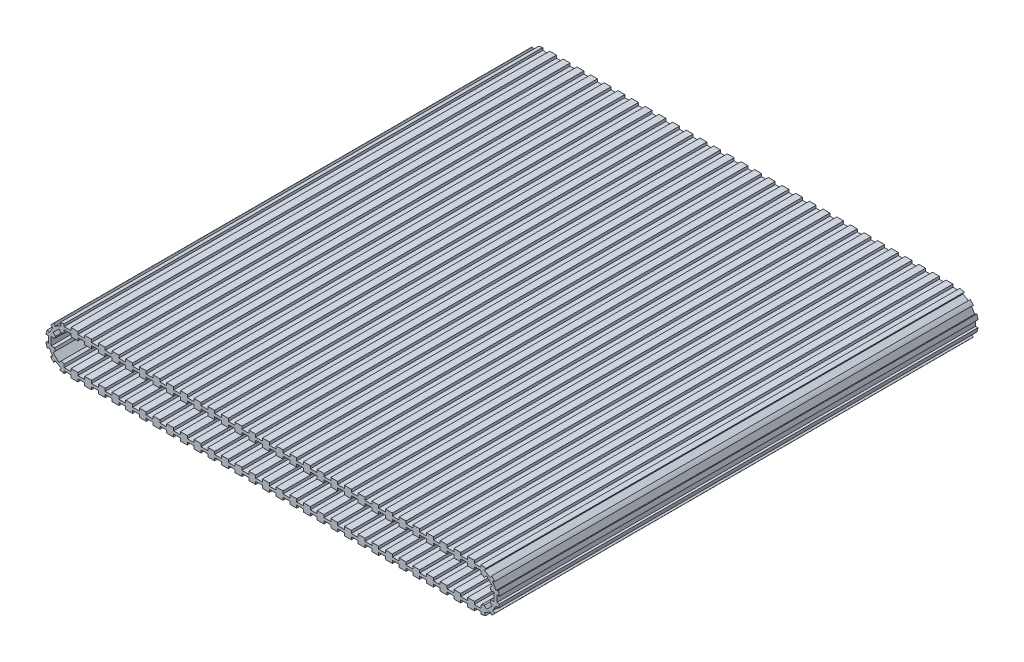
SolidWorks part; units mm, degrees
ref_plane "前视基准面" through (0, 0, 0) normal (0, 0, 1) x (1, 0, 0)
ref_plane "上视基准面" through (0, 0, 0) normal (0, 1, 0) x (1, 0, 0)
ref_plane "右视基准面" through (0, 0, 0) normal (1, 0, 0) x (0, 0, -1)
sketch "草图1" plane through (0, 0, 0) normal (0, 0, 1) x (1, 0, 0)
  line L0 (-150, 0) -> (150, 0) construction
  line L1 (-150, 10) -> (150, 10)
  line L2 (-150, -10) -> (150, -10)
  line L3 (-150, 0) -> (150, 0) construction
  line L4 (-150, 16) -> (150, 16)
  line L5 (-150, -16) -> (150, -16)
  arc A0 (-150, 10) -> (-150, -10) centre (-150, 0) ccw
  arc A1 (150, -10) -> (150, 10) centre (150, 0) ccw
  arc A2 (-150, 16) -> (-150, -16) centre (-150, 0) ccw
  arc A3 (150, -16) -> (150, 16) centre (150, 0) ccw
  point P3 (0, 0)
  point P8 (0, 0)
  dimension "D1" = 10
  dimension "D2" = 16
  dimension "D3" = 300
extrude "凸台-拉伸1" add sketch "草图1" along normal mid plane 350
sketch "草图2" plane through (0, 16, 0) normal (0, 1, 0) x (1, 0, 0)
  line L0 (150, -175) -> (-150, -175) construction
  line L5 (0, -175) -> (0, 175) construction
  line L6 (-2.5, 0) -> (2.5, 0) construction
  line L7 (7.5, 175) -> (7.5, -175)
  line L8 (7.5, 175) -> (12.5, 175)
  line L9 (12.5, 175) -> (12.5, -175)
  line L10 (7.5, -175) -> (12.5, -175)
  line L11 (17.5, 175) -> (17.5, -175)
  line L12 (17.5, 175) -> (22.5, 175)
  line L13 (22.5, 175) -> (22.5, -175)
  line L14 (17.5, -175) -> (22.5, -175)
  line L15 (27.5, 175) -> (27.5, -175)
  line L16 (27.5, 175) -> (32.5, 175)
  line L17 (32.5, 175) -> (32.5, -175)
  line L18 (27.5, -175) -> (32.5, -175)
  line L19 (37.5, 175) -> (37.5, -175)
  line L20 (37.5, 175) -> (42.5, 175)
  line L21 (42.5, 175) -> (42.5, -175)
  line L22 (37.5, -175) -> (42.5, -175)
  line L23 (47.5, 175) -> (47.5, -175)
  line L24 (47.5, 175) -> (52.5, 175)
  line L25 (52.5, 175) -> (52.5, -175)
  line L26 (47.5, -175) -> (52.5, -175)
  line L27 (57.5, 175) -> (57.5, -175)
  line L28 (57.5, 175) -> (62.5, 175)
  line L29 (62.5, 175) -> (62.5, -175)
  line L30 (57.5, -175) -> (62.5, -175)
  line L31 (67.5, 175) -> (67.5, -175)
  line L32 (67.5, 175) -> (72.5, 175)
  line L33 (72.5, 175) -> (72.5, -175)
  line L34 (67.5, -175) -> (72.5, -175)
  line L35 (77.5, 175) -> (77.5, -175)
  line L36 (77.5, 175) -> (82.5, 175)
  line L37 (82.5, 175) -> (82.5, -175)
  line L38 (77.5, -175) -> (82.5, -175)
  line L39 (87.5, 175) -> (87.5, -175)
  line L40 (87.5, 175) -> (92.5, 175)
  line L41 (92.5, 175) -> (92.5, -175)
  line L42 (87.5, -175) -> (92.5, -175)
  line L43 (97.5, 175) -> (97.5, -175)
  line L44 (97.5, 175) -> (102.5, 175)
  line L45 (102.5, 175) -> (102.5, -175)
  line L46 (97.5, -175) -> (102.5, -175)
  line L47 (107.5, 175) -> (107.5, -175)
  line L48 (107.5, 175) -> (112.5, 175)
  line L49 (112.5, 175) -> (112.5, -175)
  line L50 (107.5, -175) -> (112.5, -175)
  line L51 (117.5, 175) -> (117.5, -175)
  line L52 (117.5, 175) -> (122.5, 175)
  line L53 (122.5, 175) -> (122.5, -175)
  line L54 (117.5, -175) -> (122.5, -175)
  line L55 (127.5, 175) -> (127.5, -175)
  line L56 (127.5, 175) -> (132.5, 175)
  line L57 (132.5, 175) -> (132.5, -175)
  line L58 (127.5, -175) -> (132.5, -175)
  line L59 (137.5, 175) -> (137.5, -175)
  line L60 (137.5, 175) -> (142.5, 175)
  line L61 (142.5, 175) -> (142.5, -175)
  line L62 (137.5, -175) -> (142.5, -175)
  line L63 (147.5, 175) -> (147.5, -175)
  line L64 (147.5, 175) -> (152.5, 175)
  line L65 (152.5, 175) -> (152.5, -175)
  line L66 (147.5, -175) -> (152.5, -175)
  line L67 (-147.5, -175) -> (-152.5, -175)
  line L68 (-152.5, 175) -> (-152.5, -175)
  line L69 (-147.5, 175) -> (-152.5, 175)
  line L70 (-147.5, 175) -> (-147.5, -175)
  line L71 (-137.5, -175) -> (-142.5, -175)
  line L72 (-142.5, 175) -> (-142.5, -175)
  line L73 (-137.5, 175) -> (-142.5, 175)
  line L74 (-137.5, 175) -> (-137.5, -175)
  line L75 (-127.5, -175) -> (-132.5, -175)
  line L76 (-132.5, 175) -> (-132.5, -175)
  line L77 (-127.5, 175) -> (-132.5, 175)
  line L78 (-127.5, 175) -> (-127.5, -175)
  line L79 (-117.5, -175) -> (-122.5, -175)
  line L80 (-122.5, 175) -> (-122.5, -175)
  line L81 (-117.5, 175) -> (-122.5, 175)
  line L82 (-117.5, 175) -> (-117.5, -175)
  line L83 (-107.5, -175) -> (-112.5, -175)
  line L84 (-112.5, 175) -> (-112.5, -175)
  line L85 (-107.5, 175) -> (-112.5, 175)
  line L86 (-107.5, 175) -> (-107.5, -175)
  line L87 (-97.5, -175) -> (-102.5, -175)
  line L88 (-102.5, 175) -> (-102.5, -175)
  line L89 (-97.5, 175) -> (-102.5, 175)
  line L90 (-97.5, 175) -> (-97.5, -175)
  line L91 (-87.5, -175) -> (-92.5, -175)
  line L92 (-92.5, 175) -> (-92.5, -175)
  line L93 (-87.5, 175) -> (-92.5, 175)
  line L94 (-87.5, 175) -> (-87.5, -175)
  line L95 (-77.5, -175) -> (-82.5, -175)
  line L96 (-82.5, 175) -> (-82.5, -175)
  line L97 (-77.5, 175) -> (-82.5, 175)
  line L98 (-77.5, 175) -> (-77.5, -175)
  line L99 (-67.5, -175) -> (-72.5, -175)
  line L100 (-72.5, 175) -> (-72.5, -175)
  line L101 (-67.5, 175) -> (-72.5, 175)
  line L102 (-67.5, 175) -> (-67.5, -175)
  line L103 (-57.5, -175) -> (-62.5, -175)
  line L104 (-62.5, 175) -> (-62.5, -175)
  line L105 (-57.5, 175) -> (-62.5, 175)
  line L106 (-57.5, 175) -> (-57.5, -175)
  line L107 (-47.5, -175) -> (-52.5, -175)
  line L108 (-52.5, 175) -> (-52.5, -175)
  line L109 (-47.5, 175) -> (-52.5, 175)
  line L110 (-47.5, 175) -> (-47.5, -175)
  line L111 (-37.5, -175) -> (-42.5, -175)
  line L112 (-42.5, 175) -> (-42.5, -175)
  line L113 (-37.5, 175) -> (-42.5, 175)
  line L114 (-37.5, 175) -> (-37.5, -175)
  line L115 (-27.5, -175) -> (-32.5, -175)
  line L116 (-32.5, 175) -> (-32.5, -175)
  line L117 (-27.5, 175) -> (-32.5, 175)
  line L118 (-27.5, 175) -> (-27.5, -175)
  line L119 (-17.5, -175) -> (-22.5, -175)
  line L120 (-22.5, 175) -> (-22.5, -175)
  line L121 (-17.5, 175) -> (-22.5, 175)
  line L122 (-17.5, 175) -> (-17.5, -175)
  line L123 (-7.5, -175) -> (-12.5, -175)
  line L124 (-12.5, 175) -> (-12.5, -175)
  line L125 (-7.5, 175) -> (-12.5, 175)
  line L126 (-7.5, 175) -> (-7.5, -175)
  line L127 (-2.5, 175) -> (-2.5, -175)
  line L128 (2.5, 175) -> (2.5, -175)
  line L129 (-2.5, -175) -> (2.5, -175)
  line L130 (-2.5, 175) -> (2.5, 175)
  point P0 (0, 0)
  dimension "D1" = 5
extrude "切除-拉伸1" cut sketch "草图2" against normal blind 2
mirror "镜向1" about plane through (0, 0, 0) normal (0, 1, 0) of "切除-拉伸1"
ref_plane "基准面1" through (166, 0, 0) normal (1, 0, 0) x (0, 0, -1)
sketch "草图3" plane through (166, 0, 0) normal (1, 0, 0) x (0, 0, -1)
  line L0 (175, -15.8035) -> (175, 15.8035) construction
  line L1 (-175, 2.5) -> (175, 2.5)
  line L2 (-175, 2.5) -> (-175, -2.5)
  line L3 (-175, -2.5) -> (175, -2.5)
  line L4 (175, 2.5) -> (175, -2.5)
  line L5 (0, -2.5) -> (0, 2.5) construction
  line L6 (-175, 0) -> (175, 0) construction
  point P0 (0, 0)
  dimension "D1" = 5
extrude "切除-拉伸2" cut sketch "草图3" against normal blind 2
pattern_circular "阵列(圆周)1" count 3 every 30 about axis through (150, 0, 175) along (0, 0, 1) of "切除-拉伸2"
pattern_circular "阵列(圆周)2" count 3 every 30 about axis through (150, 0, 175) along (0, 0, 1) of "切除-拉伸2" reverse direction yes
mirror "镜向2" about plane through (0, 0, 0) normal (1, 0, 0) of "阵列(圆周)1", "阵列(圆周)2"
ref_plane "基准面2" through (0, 13, 0) normal (0, 1, 0) x (1, 0, 0)
mirror "镜向3" about plane through (0, 13, 0) normal (0, 1, 0) of "切除-拉伸1"
ref_plane "基准面3" through (0, -13, 0) normal (0, 1, 0) x (1, 0, 0)
mirror "镜向4" about plane through (0, -13, 0) normal (0, 1, 0) of "镜向1"
sketch "草图4" plane through (0, 0, 175) normal (0, 0, 1) x (1, 0, 0)
  line L1 (158, 2.9363) -> (162, 2.9363)
  line L2 (158, 2.9363) -> (158, -2.9363)
  line L3 (158, -2.9363) -> (162, -2.9363)
  line L4 (162, 2.9363) -> (162, -2.9363)
  line L5 (160, -2.9363) -> (160, 2.9363) construction
  line L6 (158, 0) -> (162, 0) construction
  arc A0 (150, -10) -> (150, 10) centre (150, 0) ccw construction
  point P0 (160, 0)
  dimension "D1" = 2
extrude "切除-拉伸3" cut sketch "草图4" against normal through all
pattern_circular "阵列(圆周)3" count 2 every 45 about axis through (150, 0, 175) along (0, 0, 1) of "切除-拉伸3"
pattern_circular "阵列(圆周)4" count 2 every 45 about axis through (150, 0, 175) along (0, 0, 1) of "切除-拉伸3" reverse direction yes
mirror "镜向5" about plane through (0, 0, 0) normal (1, 0, 0) of "阵列(圆周)4", "阵列(圆周)3"
sketch "草图5" plane through (0, 0, 175) normal (0, 0, 1) x (1, 0, 0)
  line L1 (-152.5, 12) -> (-147.681, 12)
  line L2 (-152.5, 12) -> (-152.5, 8.909)
  line L3 (-152.5, 8.909) -> (-147.681, 8.909)
  line L4 (-147.681, 12) -> (-147.681, 8.909)
extrude "切除-拉伸4" cut sketch "草图5" against normal through all
mirror "镜向6" about plane through (0, 0, 0) normal (0, 1, 0) of "切除-拉伸4"
mirror "镜向7" about plane through (0, 0, 0) normal (1, 0, 0) of "镜向6"
